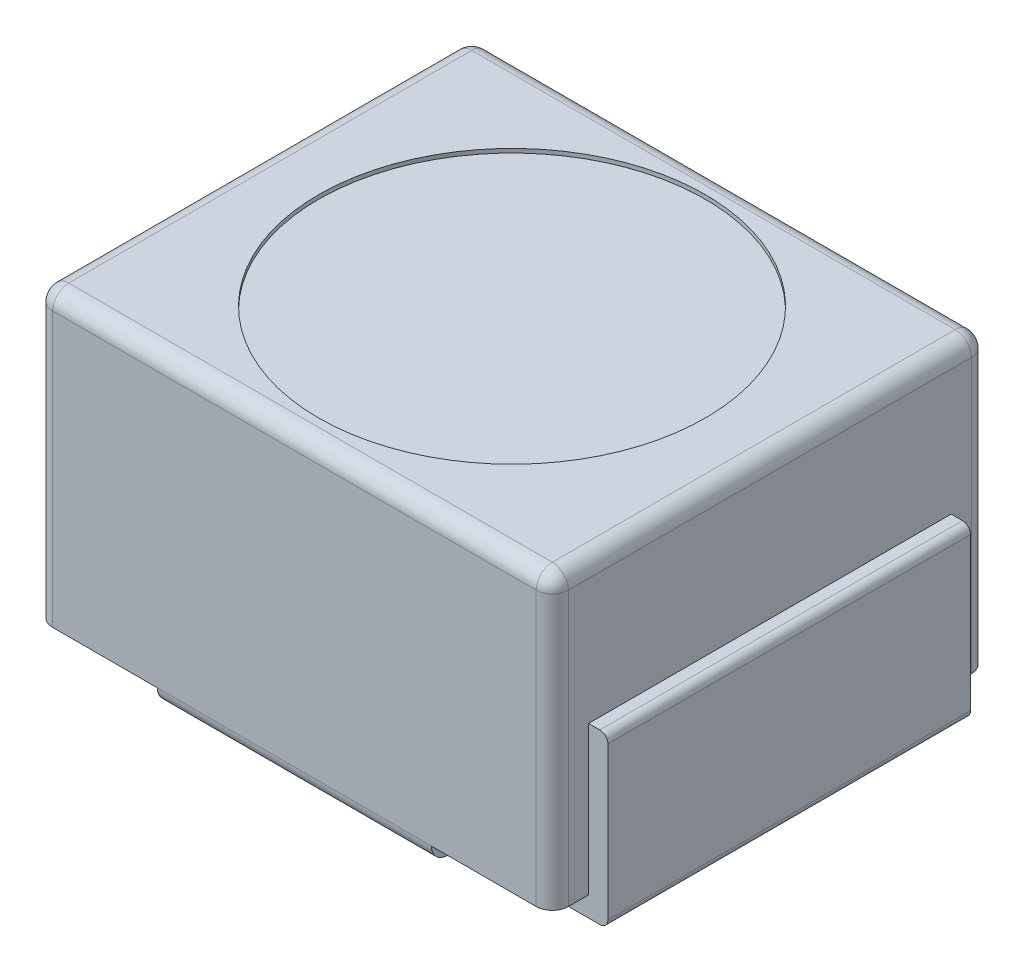
SolidWorks part; units mm, degrees
ref_plane "Спереди" through (0, 0, 0) normal (0, 0, 1) x (1, 0, 0)
ref_plane "Сверху" through (0, 0, 0) normal (0, 1, 0) x (1, 0, 0)
ref_plane "Справа" through (0, 0, 0) normal (1, 0, 0) x (0, 0, -1)
sketch "Эскиз2" plane through (0, 0, 0) normal (0, 1, 0) x (1, 0, 0)
  line L1 (-1.6, 1.35) -> (1.6, 1.35)
  line L2 (-1.6, 1.35) -> (-1.6, -1.35)
  line L3 (-1.6, -1.35) -> (1.6, -1.35)
  line L4 (1.6, 1.35) -> (1.6, -1.35)
  line L5 (-1.6, 1.35) -> (1.6, -1.35) construction
  line L6 (-1.6, -1.35) -> (1.6, 1.35) construction
  point P0 (0, 0)
  dimension "D1" = 3.2
  dimension "D2" = 2.7
extrude "Бобышка-Вытянуть1" add sketch "Эскиз2" along normal blind 1.9
fillet "Скругление1" radius 0.1 4 edges at (0, 1.9, 1.35) (-1.6, 1.9, 0) (0, 1.9, -1.35) (1.6, 1.9, 0)
fillet "Скругление2" radius 0.1 5 edges at (-1.5707, 1.8707, 1.3207) (1.5707, 1.8707, 1.3207) (0, 0, 1.35) (-1.6, 0.9, 1.35) (1.6, 0.9, 1.35)
fillet "Скругление3" radius 0.1 4 edges at (1.5707, 1.8707, -1.3207) (1.5707, 0.0293, 1.3207) (1.6, 0.9, -1.35) (1.6, 0, -0.05)
fillet "Скругление4" radius 0.1 4 edges at (-1.5707, 1.8707, -1.3207) (1.5707, 0.0293, -1.3207) (-1.6, 0.9, -1.35) (-0.05, 0, -1.35)
fillet "Скругление5" radius 0.1 3 edges at (-1.5707, 0.0293, -1.3207) (-1.5707, 0.0293, 1.3207) (-1.6, 0, 0)
sketch "Эскиз3" plane through (0, 1.9, 0) normal (0, 1, 0) x (1, 0, 0)
  circle A0 centre (0, 0) radius 1.2
extrude "Вырез-Вытянуть1" cut sketch "Эскиз3" against normal blind 0.025
sketch "Эскиз4" plane through (0, 0, 0) normal (0, -1, 0) x (1, 0, 0)
  line L0 (0, 0) -> (0, 0.1364) construction
  line L1 (0, 2.8279) -> (0, -2.2605) construction
  line L2 (0.85, -1.4164) -> (1.6778, -1.4164)
  line L3 (0.85, -1.4164) -> (0.85, 1.4195)
  line L4 (0.85, 1.4195) -> (1.6778, 1.4195)
  line L5 (1.6778, -1.4164) -> (1.6778, 1.4195)
  line L6 (-0.85, -1.4164) -> (-0.85, 1.4195)
  line L7 (-0.85, 1.4195) -> (-1.6778, 1.4195)
  line L8 (-1.6778, -1.4164) -> (-1.6778, 1.4195)
  line L9 (-0.85, -1.4164) -> (-1.6778, -1.4164)
extrude "Вырез-Вытянуть2" cut sketch "Эскиз4" against normal blind 0.1
ref_plane "Плоскость1" through (0, 0, 0) normal (0, 0, -1) x (-1, 0, 0)
sketch "Эскиз6" plane through (0, 0, 0) normal (0, 0, -1) x (-1, 0, 0)
  line L0 (1.6, 0.1) -> (0.8706, 0.1)
  line L1 (1.5, 0.1) -> (0.85, 0.1) construction
  line L2 (0.8706, 0.1) -> (0.8706, 0.0254)
  line L3 (0.9206, -0.0246) -> (1.67, -0.0246)
  line L4 (1.6, 0.1) -> (1.6, 1.0213)
  line L5 (1.6, 1.8) -> (1.6, 0.1) construction
  line L6 (1.6, 1.0213) -> (1.67, 1.0213)
  line L7 (1.72, 0.9713) -> (1.72, 0.0254)
  line L8 (0, 0) -> (0, 0.9713) construction
  line L9 (-1.6, 1.0213) -> (-1.67, 1.0213)
  line L10 (-1.6, 0.1) -> (-1.6, 1.0213)
  line L11 (-1.6, 0.1) -> (-0.8706, 0.1)
  line L12 (-0.8706, 0.1) -> (-0.8706, 0.0254)
  line L13 (-0.9206, -0.0246) -> (-1.67, -0.0246)
  line L14 (-1.72, 0.9713) -> (-1.72, 0.0254)
  arc A0 (1.72, 0.9713) -> (1.67, 1.0213) centre (1.67, 0.9713) ccw
  arc A1 (1.72, 0.0254) -> (1.67, -0.0246) centre (1.67, 0.0254) cw
  arc A2 (0.8706, 0.0254) -> (0.9206, -0.0246) centre (0.9206, 0.0254) ccw
  arc A3 (-1.72, 0.9713) -> (-1.67, 1.0213) centre (-1.67, 0.9713) cw
  arc A4 (-0.8706, 0.0254) -> (-0.9206, -0.0246) centre (-0.9206, 0.0254) cw
  arc A5 (-1.72, 0.0254) -> (-1.67, -0.0246) centre (-1.67, 0.0254) ccw
  dimension "D1" = 0.05
extrude "Бобышка-Вытянуть3" add sketch "Эскиз6" along normal mid plane 2.25
